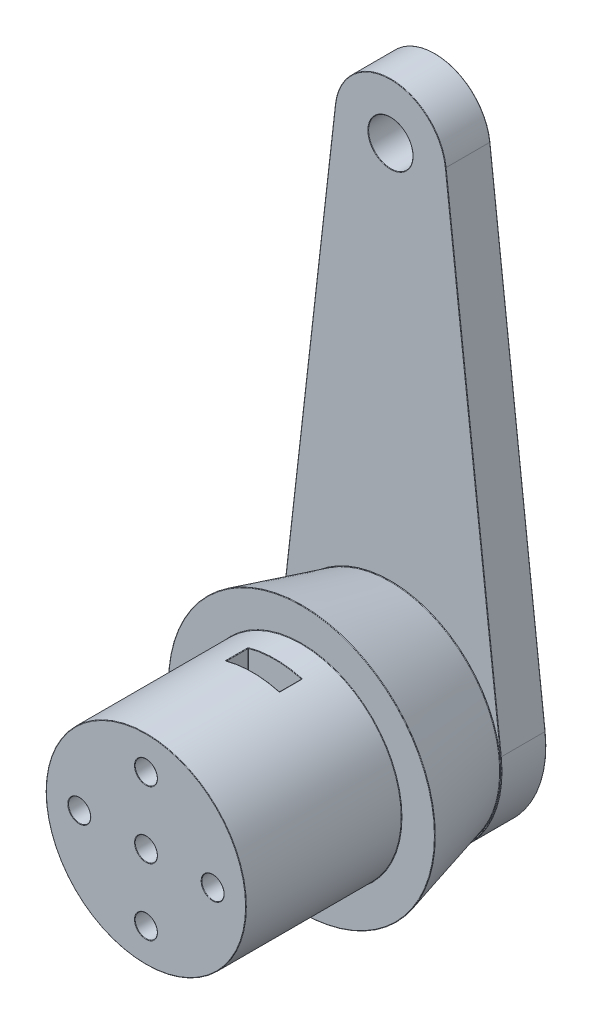
SolidWorks part; units mm, degrees
ref_plane "Front Plane" through (0, 0, 0) normal (0, 0, 1) x (1, 0, 0)
ref_plane "Top Plane" through (0, 0, 0) normal (0, 1, 0) x (1, 0, 0)
ref_plane "Right Plane" through (0, 0, 0) normal (1, 0, 0) x (0, 0, -1)
sketch "Sketch1" plane through (0, 0, 0) normal (0, 0, 1) x (1, 0, 0)
  circle A0 centre (0, 0) radius 22.5
  dimension "D1" = 45
extrude "Boss-Extrude1" add sketch "Sketch1" along normal blind 35
sketch "Sketch2" plane through (0, 0, 0) normal (0, 0, -1) x (-1, 0, 0)
  circle A0 centre (0, 0) radius 30
  dimension "D1" = 60
extrude "Boss-Extrude2" add sketch "Sketch2" along normal blind 20 draft 15
sketch "Sketch3" plane through (0, 0, -20) normal (0, 0, -1) x (-1, 0, 0)
  line L0 (0, 0) -> (0, 110) construction
  line L1 (-12.419, 111.4205) -> (-24.8381, 2.8409)
  line L2 (12.419, 111.4205) -> (24.8381, 2.8409)
  circle A0 centre (0, 0) radius 5
  arc A1 (-24.8381, 2.8409) -> (24.8381, 2.8409) centre (0, 0) ccw
  circle A2 centre (0, 110) radius 5
  arc A3 (12.419, 111.4205) -> (-12.419, 111.4205) centre (0, 110) ccw
  dimension "D1" = 10
  dimension "D2" = 50
  dimension "D3" = 10
  dimension "D4" = 25
  dimension "D5" = 110
extrude "Boss-Extrude3" add sketch "Sketch3" along normal blind 10
sketch "Sketch5" plane through (0, 0, -30) normal (0, 0, -1) x (-1, 0, 0)
  circle A0 centre (0, 0) radius 5 construction
  circle A1 centre (0, 0) radius 5
extrude "Cut-Extrude2" cut sketch "Sketch5" against normal blind 60 and the other way through all
sketch "Sketch6" plane through (0, 0, 30) normal (0, 0, -1) x (-1, 0, 0)
  circle A0 centre (0, 0) radius 2.5
  dimension "D1" = 5
extrude "Cut-Extrude3" cut sketch "Sketch6" against normal blind 60
ref_plane "Plane1" through (0, 22.5, 0) normal (0, 1, 0) x (1, 0, 0)
sketch "Sketch7" plane through (0, 22.5, 0) normal (0, 1, 0) x (1, 0, 0)
  line L0 (0, 30) -> (0, -25)
  line L1 (12.419, 30) -> (-12.419, 30) construction
  line L3 (-6, -6) -> (6, -6)
  line L4 (-6, -6) -> (-6, -11)
  line L5 (-6, -11) -> (6, -11)
  line L6 (6, -6) -> (6, -11)
  point P9 (0, -6)
  dimension "D1" = 55
  dimension "D2" = 12
  dimension "D3" = 5
  dimension "D4" = 14
extrude "Cut-Extrude4" cut sketch "Sketch7" against normal blind 27 contours L4 L3 L6 L5
sketch "Sketch9" plane through (0, 0, 35) normal (0, 0, 1) x (1, 0, 0)
  line L0 (0, 0) -> (0, 15) construction
  line L1 (0, 0) -> (15, 0) construction
  line L2 (0, 0) -> (0, -15) construction
  line L3 (0, 0) -> (-15, 0) construction
  circle A0 centre (0, 15) radius 2.5
  circle A1 centre (15, 0) radius 2.5
  circle A2 centre (0, -15) radius 2.5
  circle A3 centre (-15, 0) radius 2.5
  circle A4 centre (0, 0) radius 22.5 construction
  point P13 (0, 0)
  dimension "D2" = 5
  dimension "D1" = 15
  dimension "D3" = 4
extrude "Cut-Extrude5" cut sketch "Sketch9" against normal blind 13
fillet "Fillet2" radius 0.1 37 edges at (0, 122.5, -20) (6, 8.5926, 11) (6, -4.5, 8.5) (6, 8.5926, 6) (4.0897, -4.5, 6) (-4.0897, -4.5, 6) (-6, 8.5926, 6) (-6, -4.5, 8.5) (-6, 8.5926, 11) (-5, 0, 30) (0, 5, 11) (-2.1794, -4.5, 8.5) (0, 5, 6) (2.1794, -4.5, 8.5) (-5, 110, -20) (18.6285, 57.1307, -20) (0, -25, -20) (-18.6285, 57.1307, -20) (-5, 110, -30) (18.6285, 57.1307, -30) (0, 122.5, -30) (-18.6285, 57.1307, -30) (0, -25, -30) (-5, 0, -30) (-30, 0, 0) (-24.641, 0, -20) (-6, 21.6852, 8.5) (0, 22.5, 11) (6, 21.6852, 8.5) (0, 22.5, 6) (22.5, 0, 0) (22.5, 0, 35) (2.5, 0, 35) (-12.5, 0, 35) (2.5, -15, 35) (17.5, 0, 35) (2.5, 15, 35)
